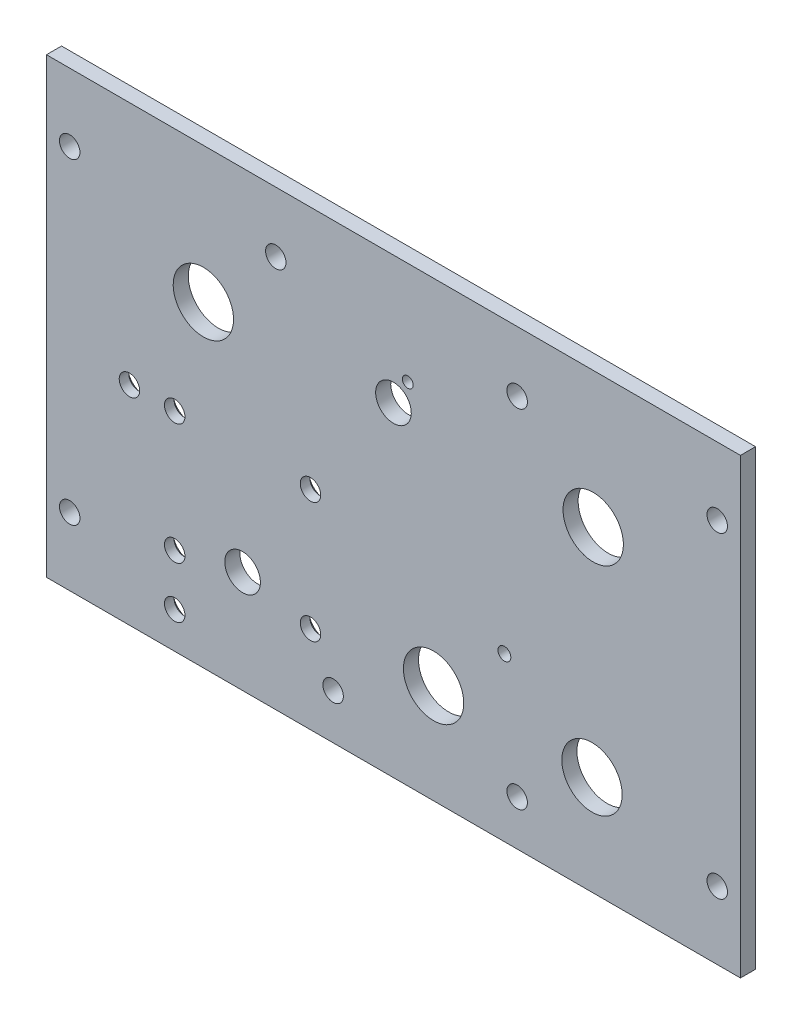
SolidWorks part; units mm, degrees
material "Acrylic (Medium-high impact)"
ref_plane "Front Plane" through (0, 0, 0) normal (0, 0, 1) x (1, 0, 0)
ref_plane "Top Plane" through (0, 0, 0) normal (0, 1, 0) x (1, 0, 0)
ref_plane "Right Plane" through (0, 0, 0) normal (1, 0, 0) x (0, 0, -1)
sketch "Sketch1" plane through (0, 0, 0) normal (0, 0, 1) x (1, 0, 0)
  line L8 (0, 95.25) -> (-146.05, 95.25)
  line L9 (-146.05, 95.25) -> (-146.05, 0)
  line L10 (-146.05, 0) -> (0, 0)
  line L11 (0, 0) -> (0, 95.25)
extrude "Boss-Extrude1" add sketch "Sketch1" against normal blind 3.175
hole_wizard "#6 Clearance Hole1" positions "Sketch3" profile "Sketch2" hole size "#6" standard "ANSI Inch" end condition through all
sketch "Sketch3" plane through (0, 0, -3.175) normal (0, 0, -1) x (-1, 0, 0)
  point P0 (4.8895, 80.9625)
  point P3 (141.1605, 80.9625)
  point P6 (141.1605, 14.2875)
  point P9 (4.8895, 14.2875)
  point P12 (46.99, 9.525)
  point P15 (85.725, 9.525)
  point P18 (97.79, 82.55)
  point P21 (46.99, 82.55)
sketch "Sketch2" plane through (-4.8895, 80.9625, -3.175) normal (1, 0, 0) x (0, 1, 0)
  line L0 (0, 0) -> (0, 3.175)
  line L1 (0, 3.175) -> (2.1526, 3.175)
  line L2 (2.1526, 3.175) -> (2.1526, 0)
  line L5 (2.1526, 0) -> (0, 0)
  line L11 (0, -6.35) -> (0, 107.95) construction
  dimension "Thru Hole Dia." = 4.3053
  dimension "Thru Hole Depth" = 3.175
sketch "Sketch5" plane through (0, 0, -7.4676) normal (0, 0, -1) x (-1, 0, 0)
  circle A0 centre (30.988, 66.675) radius 6.35
  circle A1 centre (113.03, 66.675) radius 6.35
  circle A2 centre (64.5795, 20.955) radius 6.35
  circle A3 centre (31.242, 20.955) radius 6.35
  circle A4 centre (73.025, 68.326) radius 3.75
  circle A5 centre (104.775, 21.59) radius 3.75
  dimension "D1" = 12.7
  dimension "D2" = 7.5
extrude "Cut-Extrude1" cut sketch "Sketch5" against normal through all
hole_wizard "CSK for #6 Flat Head Machine Screw (100)1" positions "Sketch7" profile "Sketch6" countersink size "#6" standard "ANSI Inch" end condition through all
sketch "Sketch7" plane through (0, 0, -3.175) normal (0, 0, -1) x (-1, 0, 0)
  point P0 (90.4875, 43.815)
  point P3 (90.4875, 18.415)
  point P6 (119.0625, 7.6362)
  point P9 (119.0625, 18.415)
  point P12 (119.0625, 43.815)
  point P15 (128.5875, 43.815)
sketch "Sketch6" plane through (-90.4875, 43.815, -3.175) normal (1, 0, 0) x (0, 1, 0)
  line L0 (0, 0) -> (0, 3.175)
  line L1 (0, 3.175) -> (2.1526, 3.175)
  line L2 (2.1526, 3.175) -> (2.1526, 1.1669)
  line L3 (2.1526, 1.1669) -> (3.5433, 0)
  line L5 (3.5433, 0) -> (0, 0)
  line L6 (-2.1526, 1.1669) -> (-3.5433, 0) construction
  line L11 (0, -6.35) -> (0, 107.95) construction
  dimension "Thru Hole Dia." = 4.3053
  dimension "Thru Hole Depth" = 3.175
  dimension "Near C'Sink Dia." = 7.0866
  dimension "Near C'Sink Angle" = 100
sketch "Sketch8" plane through (0, 0, 0) normal (0, 0, 1) x (1, 0, 0)
  circle A0 centre (-70.0124, 73.6066) radius 1.1345
extrude "Cut-Extrude2" cut sketch "Sketch8" against normal through all
hole_wizard "CSK for #2 Flat Head Machine Screw (100)1" positions "Sketch13" profile "Sketch14" countersink size "#2" standard "ANSI Inch" end condition through all
sketch "Sketch13" plane through (0, 0, -3.175) normal (0, 0, -1) x (-1, 0, 0)
  point P3 (49.68, 34.2646)
  point P12 (0, 0)
  point P13 (0, 0)
  point P14 (0, 0)
  point P15 (0, 0)
sketch "Sketch14" plane through (-49.68, 34.2646, -3.175) normal (1, 0, 0) x (0, 1, 0)
  line L0 (0, 0) -> (0, 3.175)
  line L1 (0, 3.175) -> (1.3525, 3.175)
  line L2 (1.3525, 3.175) -> (1.3525, 0.698)
  line L3 (1.3525, 0.698) -> (2.1844, 0)
  line L5 (2.1844, 0) -> (0, 0)
  line L6 (-1.3525, 0.698) -> (-2.1844, 0) construction
  line L11 (0, -6.35) -> (0, 107.95) construction
  dimension "Thru Hole Dia." = 2.7051
  dimension "Thru Hole Depth" = 3.175
  dimension "Near C'Sink Dia." = 4.3688
  dimension "Near C'Sink Angle" = 100
